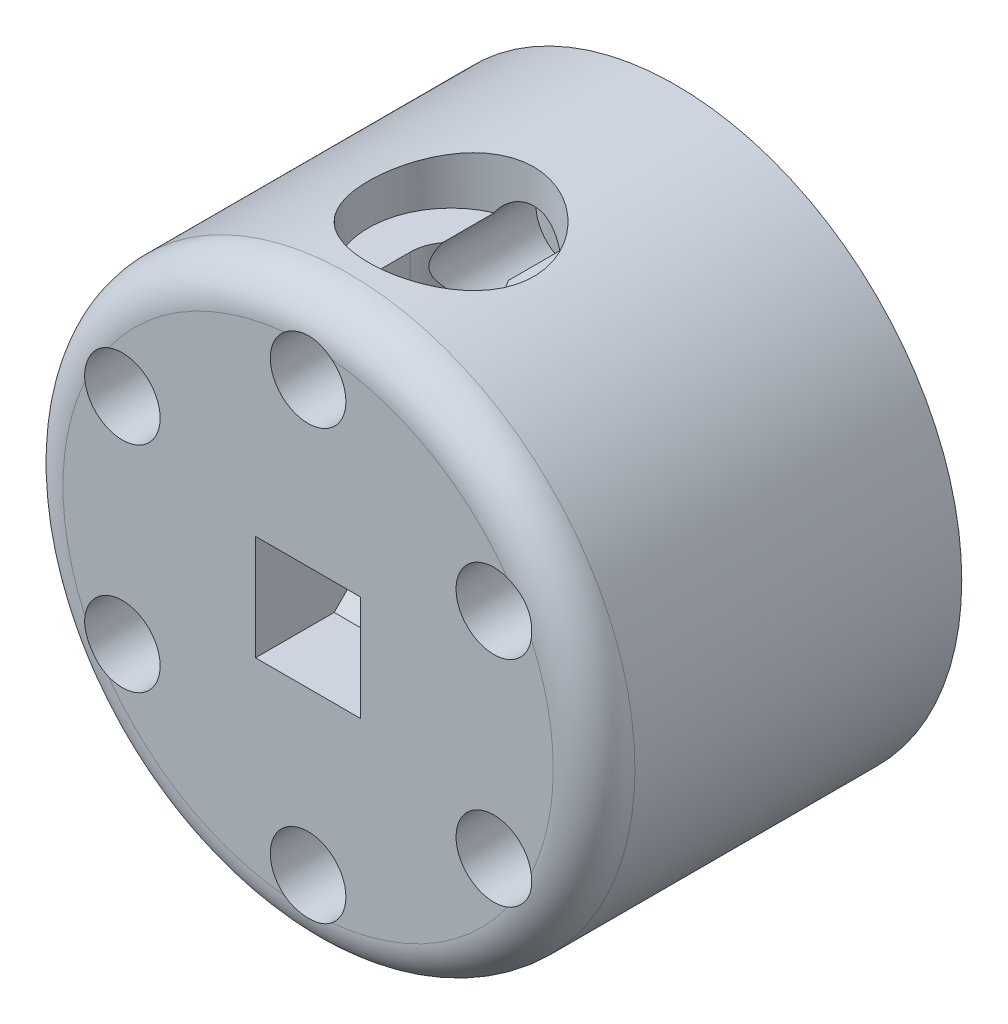
SolidWorks part; units mm, degrees
material "ABS"
ref_plane "前视基准面" through (0, 0, 0) normal (0, 0, 1) x (1, 0, 0)
ref_plane "上视基准面" through (0, 0, 0) normal (0, 1, 0) x (1, 0, 0)
ref_plane "右视基准面" through (0, 0, 0) normal (1, 0, 0) x (0, 0, -1)
sketch "草图1" plane through (0, 0, 0) normal (0, 0, 1) x (1, 0, 0)
  circle A0 centre (0, 0) radius 14
  dimension "D1" = 28
extrude "凸台-拉伸1" add sketch "草图1" along normal blind 22
sketch "草图2" plane through (0, 0, 22) normal (0, 0, 1) x (1, 0, 0)
  line L1 (0, 10.5) -> (-9.0933, 5.25) construction
  line L2 (-9.0933, 5.25) -> (-9.0933, -5.25) construction
  line L3 (-9.0933, -5.25) -> (0, -10.5) construction
  line L4 (0, -10.5) -> (9.0933, -5.25) construction
  line L5 (9.0933, -5.25) -> (9.0933, 5.25) construction
  line L6 (9.0933, 5.25) -> (0, 10.5) construction
  circle A0 centre (0, 0) radius 10.5 construction
  circle A1 centre (-9.0933, -5.25) radius 1.1
  circle A2 centre (-9.0933, 5.25) radius 1.1
  circle A3 centre (0, 10.5) radius 1.1
  circle A4 centre (9.0933, 5.25) radius 1.1
  circle A5 centre (9.0933, -5.25) radius 1.1
  circle A6 centre (0, -10.5) radius 1.1
  dimension "D1" = 21
  dimension "D2" = 2.2
sketch "草图3" plane through (0, 0, 0) normal (0, 0, -1) x (-1, 0, 0)
  circle A0 centre (0, 0) radius 7.35
  dimension "D1" = 14.7
extrude "切除-拉伸1" cut sketch "草图3" against normal blind 6
extrude "切除-拉伸2" cut sketch "草图2" against normal blind 32
sketch "草图4" plane through (0, 0, 22) normal (0, 0, 1) x (1, 0, 0)
  circle A7 centre (9.0933, 5.25) radius 1.85
  circle A8 centre (9.0933, -5.25) radius 1.85
  circle A9 centre (0, -10.5) radius 1.85
  circle A10 centre (-9.0933, -5.25) radius 1.85
  circle A11 centre (-9.0933, 5.25) radius 1.85
  circle A12 centre (0, 10.5) radius 1.85
  dimension "D1" = 3.7
extrude "切除-拉伸3" cut sketch "草图4" against normal blind 17
sketch "草图5" plane through (0, 0, 22) normal (0, 0, 1) x (1, 0, 0)
  line L1 (-2.575, -2.575) -> (2.575, -2.575)
  line L2 (-2.575, -2.575) -> (-2.575, 2.575)
  line L3 (-2.575, 2.575) -> (2.575, 2.575)
  line L4 (2.575, -2.575) -> (2.575, 2.575)
  line L5 (-2.575, -2.575) -> (2.575, 2.575) construction
  line L6 (-2.575, 2.575) -> (2.575, -2.575) construction
  point P0 (0, 0)
  dimension "D1" = 5.15
  dimension "D2" = 5.15
extrude "切除-拉伸4" cut sketch "草图5" against normal blind 13
sketch "草图6" plane through (-2.575, 0, 0) normal (1, 0, 0) x (0, 0, -1)
  line L0 (-9, -2.575) -> (-14.15, -2.575)
  line L1 (-9, -2.575) -> (-22, -2.575) construction
  line L2 (-14.15, -2.575) -> (-9, 2.575)
  line L3 (-9, 2.575) -> (-9, -2.575)
  dimension "D1" = 45
extrude "凸台-拉伸2" add sketch "草图6" along normal up to next
sketch "草图9" plane through (0, 2.575, 0) normal (0, -1, 0) x (-1, 0, 0)
  line L0 (0, -11) -> (0, -13) construction
  line L1 (2, -11) -> (2, -13)
  line L2 (-2, -11) -> (-2, -13)
  line L4 (-2.575, -9) -> (2.575, -9) construction
  arc A0 (2, -11) -> (-2, -11) centre (0, -11) ccw
  arc A1 (-2, -13) -> (2, -13) centre (0, -13) ccw
  point P3 (0, -12)
  dimension "D1" = 2
  dimension "D2" = 2
  dimension "D3" = 2
extrude "切除-拉伸7" cut sketch "草图9" against normal blind 20
sketch "草图10" plane through (0, 0, 22) normal (0, 0, 1) x (1, 0, 0)
  line L0 (4, 13.4164) -> (-4, 13.4164) construction
  line L1 (2.575, 2.575) -> (-2.575, 2.575) construction
  circle A0 centre (0, 0) radius 14 construction
  dimension "D1" = 0
  dimension "D2" = 8
ref_plane "基准面1" through (0, 13.4164, 0) normal (0, 1, 0) x (1, 0, 0)
sketch "草图11" plane through (0, 13.4164, 0) normal (0, 1, 0) x (1, 0, 0)
  circle A0 centre (0, -11) radius 4.05
  arc A1 (2, -11) -> (-2, -11) centre (0, -11) ccw construction
  point P5 (0, 0)
  dimension "D1" = 8.1
  dimension "D2" = 0
extrude "切除-拉伸8" cut sketch "草图11" along normal mid plane 4
sketch "草图12" plane through (0, 0, 22) normal (0, 0, 1) x (1, 0, 0)
  circle A0 centre (0, 0) radius 19.2084
extrude "切除-拉伸9" cut sketch "草图12" against normal blind 4
sketch "草图13" plane through (0, 2.575, 0) normal (0, -1, 0) x (-1, 0, 0)
  circle A0 centre (0, -11) radius 1.5
  dimension "D1" = 3
extrude "切除-拉伸10" cut sketch "草图13" along normal blind 23
fillet "圆角1" radius 2 1 edges at (14, 0, 18)
